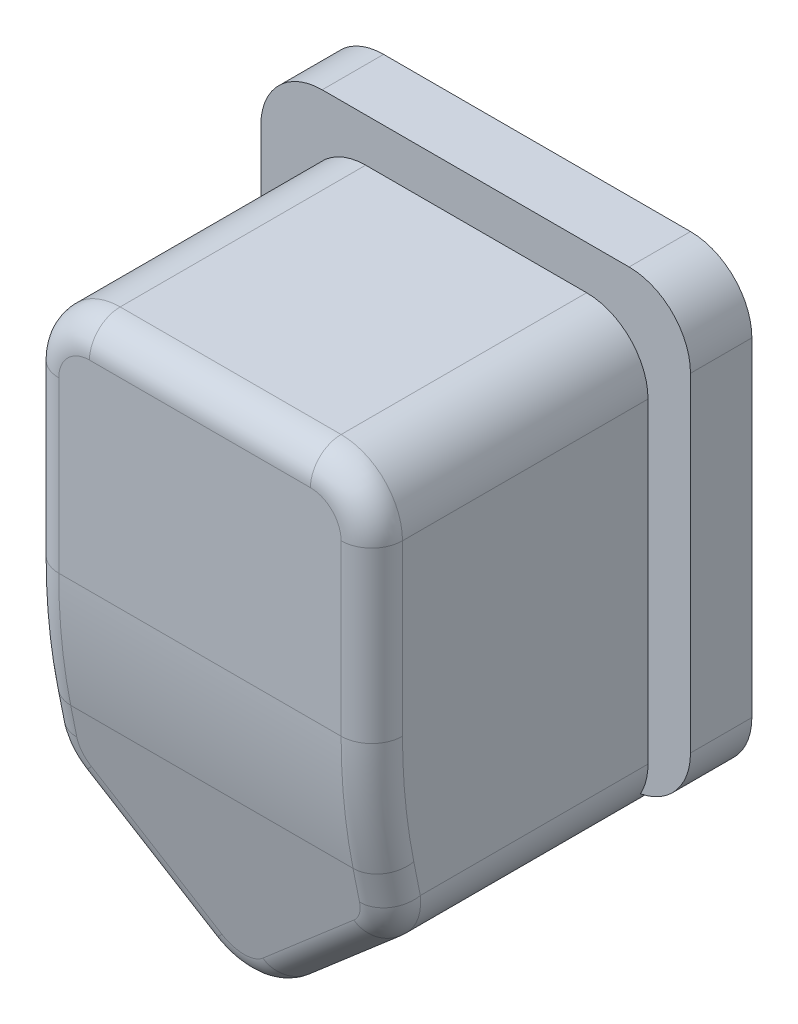
SolidWorks part; units mm, degrees
ref_plane "Front Plane" through (0, 0, 0) normal (0, 0, 1) x (1, 0, 0)
ref_plane "Top Plane" through (0, 0, 0) normal (0, 1, 0) x (1, 0, 0)
ref_plane "Right Plane" through (0, 0, 0) normal (1, 0, 0) x (0, 0, -1)
sketch "草图1" plane through (0, 0, 0) normal (0, 0, 1) x (1, 0, 0)
  line L0 (-2.4632, -3.5693) -> (-0.6643, -5.1984)
  line L2 (2.8081, -2.8598) -> (2.8081, 2.2905)
  line L3 (1.8081, 3.2905) -> (-1.7919, 3.2905)
  line L4 (-2.7919, -2.828) -> (-2.7919, 2.2905)
  line L5 (2.8081, -3.3095) -> (-2.7919, 3.2905) construction
  line L6 (2.8081, 3.2905) -> (-2.7919, -3.2715) construction
  line L7 (0.6705, -5.2053) -> (2.4716, -3.6079)
  arc A0 (0.6705, -5.2053) -> (-0.6643, -5.1984) centre (0.007, -4.4572) cw
  arc A1 (-2.7919, -2.828) -> (-2.4632, -3.5693) centre (-1.7919, -2.828) ccw
  arc A2 (2.8081, -2.8598) -> (2.4716, -3.6079) centre (1.8081, -2.8598) cw
  arc A3 (1.8081, 3.2905) -> (2.8081, 2.2905) centre (1.8081, 2.2905) cw
  arc A4 (-2.7919, 2.2905) -> (-1.7919, 3.2905) centre (-1.7919, 2.2905) cw
  point P0 (0, 0)
  point P9 (0, -5.8)
  dimension "D4" = 1
  dimension "D1" = 5.6
  dimension "D2" = 6.6
  dimension "D3" = 5.8
extrude "凸台-拉伸1" add sketch "草图1" along normal blind 5.5
sketch "草图2" plane through (0, 0, 0) normal (0, 0, -1) x (-1, 0, 0)
  line L2 (3.5, -2.3576) -> (3.5, 3)
  line L3 (2.5, 4) -> (-2.5, 4)
  line L4 (-3.5, -2.3576) -> (-3.5, 3)
  line L5 (3.3697, -3.8511) -> (-3.5, 4) construction
  line L6 (3.5, 4) -> (-3.5, -4) construction
  line L8 (-2.5, -3.3576) -> (2.5, -3.3576)
  arc A3 (3.5, 3) -> (2.5, 4) centre (2.5, 3) ccw
  arc A4 (-2.5, 4) -> (-3.5, 3) centre (-2.5, 3) ccw
  arc A5 (3.5, -2.3576) -> (2.5, -3.3576) centre (2.5, -2.3576) cw
  arc A6 (-3.5, -2.3576) -> (-2.5, -3.3576) centre (-2.5, -2.3576) ccw
  point P0 (0, 0)
  point P9 (0, -5.6)
  dimension "D2" = 1
  dimension "D1" = 7
  dimension "D3" = 5.6
extrude "凸台-拉伸2" add sketch "草图2" against normal blind 1
sketch "草图3" plane through (0, 0, 0) normal (0, 0, -1) x (-1, 0, 0)
  line L0 (0, 4.248) -> (0, -7.3544) construction
  line L1 (2.5, 4) -> (-2.5, 4) construction
  line L2 (-1.9, 1.8) -> (-1.9, -1)
  line L3 (1.9, 1.8) -> (1.9, -1)
  arc A0 (1.9, 1.8) -> (-1.9, 1.8) centre (0, 1.8) ccw
  arc A1 (-1.9, -1) -> (1.9, -1) centre (0, -1) ccw
  dimension "D1" = 2.2
  dimension "D3" = 1.9
  dimension "D2" = 5
extrude "切除-拉伸1" cut sketch "草图3" against normal blind 0.5
sketch "草图4" plane through (-2.7919, 0, 0) normal (-1, 0, 0) x (0, 0, 1)
  line L0 (5.5, -1.4572) -> (4.7, -5.4572)
  line L1 (5.5, 2.2905) -> (5.5, -2.828) construction
  line L2 (0, -5.4572) -> (5.5, -5.4572) construction
  line L3 (4.7, -5.4572) -> (5.5, -5.4572)
  line L4 (5.5, -5.4572) -> (5.5, -5.1984) construction
  line L5 (5.5, -5.4572) -> (5.5, -1.4572)
  dimension "D1" = 4
  dimension "D2" = 0.8
extrude "切除-拉伸2" cut sketch "草图4" against normal blind 11
fillet "圆角1" radius 10 1 edges at (0.0081, -1.4572, 5.5)
fillet "圆角2" radius 0.5 14 edges at (2.8081, -2.644, 5.2626) (2.7201, -3.27, 5.1374) (2.8081, -1.4524, 5.4513) (2.8081, 0.9117, 5.5) (2.5152, 2.9976, 5.5) (0.0081, 3.2905, 5.5) (-2.499, 2.9976, 5.5) (1.5711, -4.4066, 4.9101) (0.0018, -5.4572, 4.7) (-1.5637, -4.3838, 4.9147) (-2.7919, -2.6281, 5.2658) (-2.7061, -3.2335, 5.1447) (-2.7919, -1.4524, 5.4513) (-2.7919, 0.9117, 5.5)
